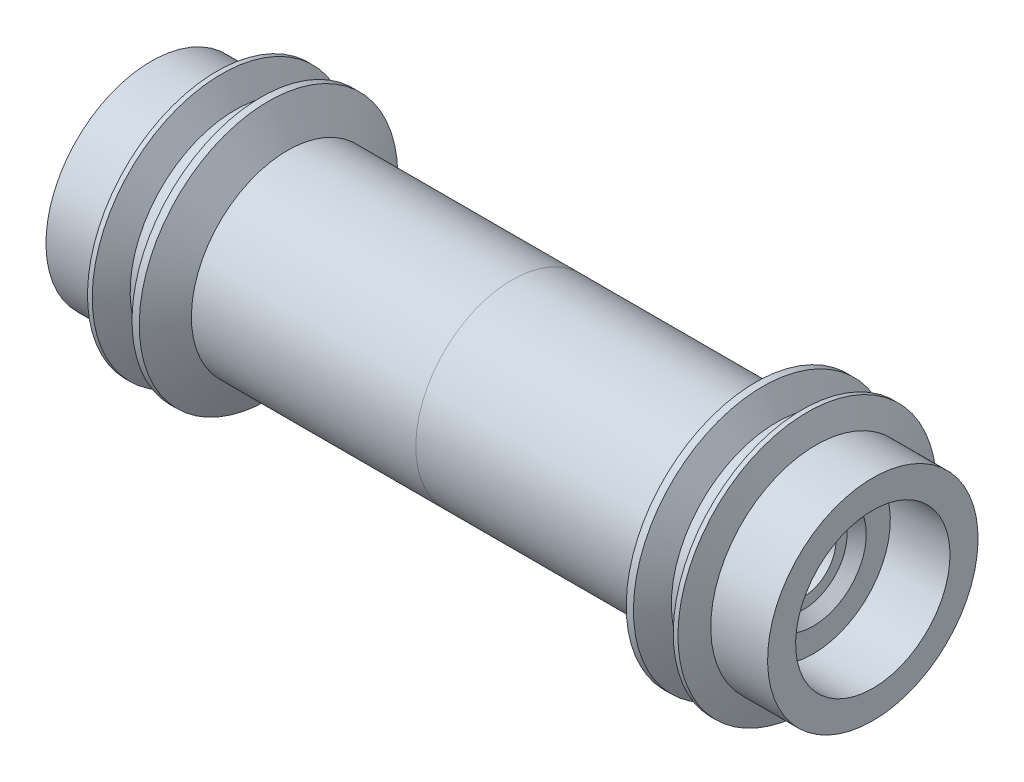
SolidWorks part; units mm, degrees
ref_plane "Front Plane" through (0, 0, 0) normal (0, 0, 1) x (1, 0, 0)
ref_plane "Top Plane" through (0, 0, 0) normal (0, 1, 0) x (1, 0, 0)
ref_plane "Right Plane" through (0, 0, 0) normal (1, 0, 0) x (0, 0, -1)
sketch "Sketch2" plane through (0, 0, 0) normal (0, 0, 1) x (1, 0, 0)
  line L0 (0, 0) -> (0, 28.4375) construction
  line L1 (-19.05, 4.075) -> (-15.9, 4.075) construction
  line L2 (-19.05, 4.075) -> (-19.05, -4.075) construction
  line L3 (-19.05, -4.075) -> (-15.9, -4.075) construction
  line L4 (-15.9, 4.075) -> (-15.9, -4.075) construction
  line L5 (-19.05, 4.075) -> (-15.9, -4.075) construction
  line L6 (-19.05, -4.075) -> (-15.9, 4.075) construction
  line L7 (15.9, 4.5) -> (47.6832, 4.5) construction
  line L8 (15.9, 4.5) -> (15.9, -4.5) construction
  line L9 (15.9, -4.5) -> (47.6832, -4.5) construction
  line L10 (47.6832, 4.5) -> (47.6832, -4.5) construction
  line L11 (15.9, 4.5) -> (47.6832, -4.5) construction
  line L12 (15.9, -4.5) -> (47.6832, 4.5) construction
  line L13 (-19.05, 0) -> (47.6832, 0) construction
  line L14 (-19.05, 5.5562) -> (-16.05, 5.5562)
  line L15 (-16.05, 5.5562) -> (-15.5878, 6.8262)
  line L16 (-15.5878, 6.8262) -> (-15.3382, 6.8262)
  line L19 (-13.2368, 6.8262) -> (-12.8558, 6.8262)
  line L20 (-12.8558, 6.8262) -> (-11.8476, 5.08)
  line L21 (-11.8476, 5.08) -> (0, 5.08)
  line L22 (-19.05, 5.5562) -> (-19.05, 4.075)
  line L23 (-19.05, 4.075) -> (-15.9, 4.075)
  line L24 (-15.9, 4.075) -> (-15.9, 0)
  line L25 (-15.9, 0) -> (0, 0)
  line L26 (0, 0) -> (0, 5.08)
  line L27 (-33.5594, -5.5562) -> (-33.5594, 5.5562) construction
  line L28 (-14.2875, 5.5562) -> (-14.2875, 7.68) construction
  line L29 (-14.2875, 5.5562) -> (14.2875, 5.5562) construction
  line L30 (-19.05, 5.5562) -> (19.05, 5.5562) construction
  line L31 (0, 1.6) -> (-6.5, 1.6)
  line L32 (-6.5, 1.6) -> (-8.1, 0)
  line L33 (-6.5, 1.6) -> (-6.5, -1.6) construction
  line L34 (-6.5, 1.6) -> (6.5, 1.6) construction
  line L35 (-15.9, 1.7145) -> (-9.225, 1.7145)
  line L36 (-9.225, 1.7145) -> (-9.225, 0)
  line L37 (-15.9, 2.805) -> (-15.392, 2.297)
  line L38 (-9.225, 1.7145) -> (-22.225, 1.7145) construction
  line L39 (-9.225, 1.7145) -> (-9.225, -1.7145) construction
  line L40 (-9.225, -1.7145) -> (-22.225, -1.7145) construction
  line L41 (-22.225, 1.7145) -> (-22.225, -1.7145) construction
  line L42 (-15.392, 2.297) -> (-15.392, 0)
  line L43 (-15.3382, 6.8262) -> (-14.605, 5.5562)
  line L44 (-14.605, 5.5562) -> (-13.97, 5.5562)
  line L45 (-13.97, 5.5562) -> (-13.2368, 6.8262)
  point P0 (-17.475, 0)
  point P5 (31.7916, 0)
  point P27 (-33.5594, 0)
  point P28 (-13.0463, 6.8262)
  point P29 (-6.5, 0)
  point P33 (0, 5.5562)
  point P36 (0, 1.6)
  point P48 (-9.225, 0)
  point P51 (0, 5.5562)
  point P54 (-14.2875, 5.5562)
  dimension "D1" = 3.15
  dimension "D3" = 5.08
  dimension "D4" = 11.1125
  dimension "D5" = 8.15
  dimension "D6" = 60
  dimension "D7" = 60
  dimension "D8" = 1.27
  dimension "D9" = 70
  dimension "D10" = 28.575
  dimension "D11" = 38.1
  dimension "D12" = 0.381
  dimension "D13" = 45
  dimension "D14" = 13
  dimension "D15" = 3.2
  dimension "D16" = 3.429
  dimension "D17" = 3.175
  dimension "D18" = 1.27
  dimension "D19" = 0.508
  dimension "D20" = 45
  dimension "D21" = 13
  dimension "D22" = 3
  dimension "D23" = 0.635
revolve "Revolve1" add sketch "Sketch2" angle 360 about L13 region at (-8.9283, 3.5155, 0)
mirror "Mirror1" about plane through (0, 0, 0) normal (1, 0, 0) of bodies 101
chamfer "Chamfer1" distance 0.508 angle 45 1 edges at (-19.05, -4.075, 0)
